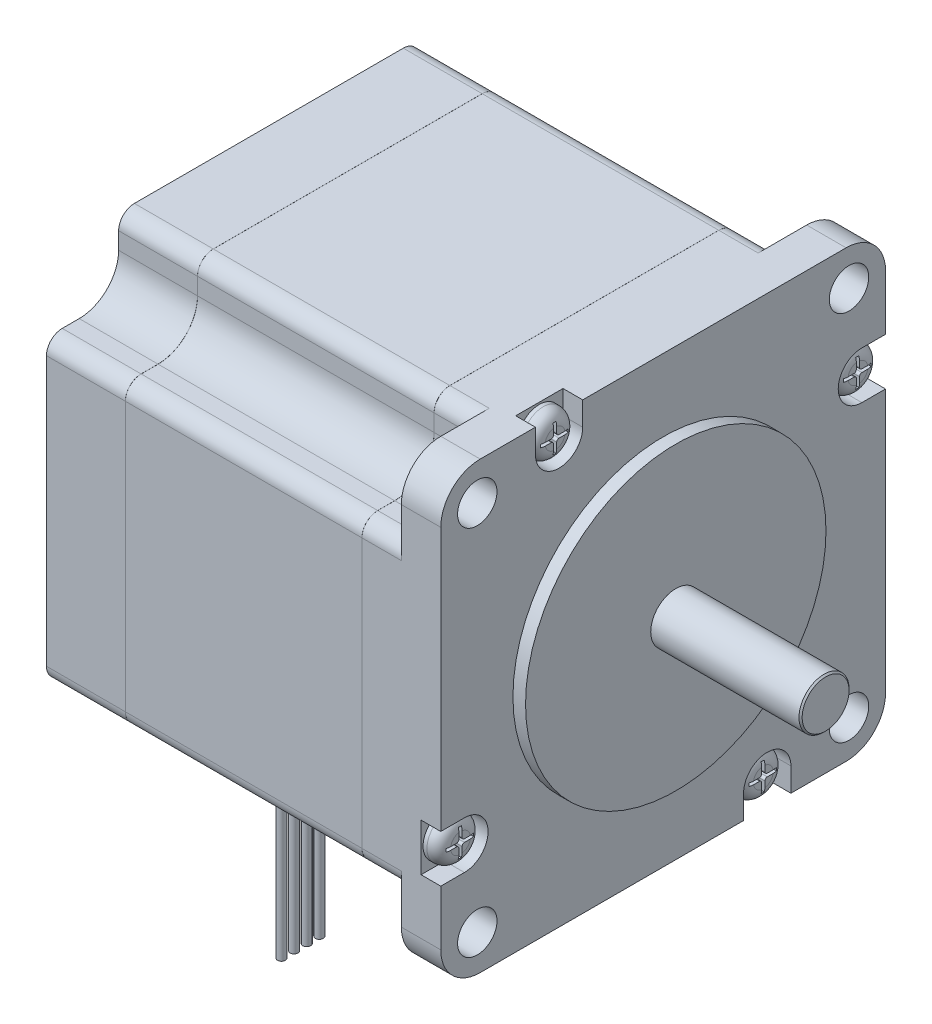
SolidWorks part; units mm, degrees
ref_plane "Front Plane" through (0, 0, 0) normal (0, 0, 1) x (1, 0, 0)
ref_plane "Top Plane" through (0, 0, 0) normal (0, 1, 0) x (1, 0, 0)
ref_plane "Right Plane" through (0, 0, 0) normal (1, 0, 0) x (0, 0, -1)
ref_axis "Axis_X" through (-43.03, 0, 0) along (1, 0, 0)
ref_axis "Axis_Y" through (0, 32.61, 0) along (0, -1, 0)
ref_axis "Axis_Z" through (0, 0, -31.02) along (0, 0, 1)
sketch "Sketch1" plane through (0, 0, 0) normal (1, 0, 0) x (0, 0, -1)
  line L1 (23.2, -28.2) -> (-23.2, -28.2)
  line L2 (28.2, -23.2) -> (28.2, 23.2)
  line L3 (23.2, 28.2) -> (-23.2, 28.2)
  line L4 (-28.2, -23.2) -> (-28.2, 23.2)
  line L5 (28.2, -28.2) -> (-28.2, 28.2) construction
  line L6 (28.2, 28.2) -> (-28.2, -28.2) construction
  arc A0 (28.2, -23.2) -> (23.2, -28.2) centre (23.2, -23.2) cw
  arc A1 (-23.2, -28.2) -> (-28.2, -23.2) centre (-23.2, -23.2) cw
  arc A2 (28.2, 23.2) -> (23.2, 28.2) centre (23.2, 23.2) ccw
  arc A3 (-28.2, 23.2) -> (-23.2, 28.2) centre (-23.2, 23.2) cw
  point P0 (0, 0)
  dimension "FIX_2" = 5
  dimension "FIX_1" = 56.4
extrude "Boss-Extrude1" add sketch "Sketch1" against normal blind 50
sketch "Sketch2" plane through (0, 0, 0) normal (0, 0, 1) x (1, 0, 0)
  line L0 (0, 0) -> (20.6, 0) construction
  line L1 (20.4, 3.175) -> (20.6, 2.975)
  line L2 (0, 0) -> (20.6, 0)
  line L3 (0, 0) -> (0, 19.05)
  line L4 (0, 19.05) -> (1.6, 19.05)
  line L5 (1.6, 3.175) -> (1.6, 19.05)
  line L6 (1.6, 3.175) -> (20.4, 3.175)
  line L9 (20.6, 2.975) -> (20.6, 0)
  dimension "FIX_3" = 38.1
  dimension "FIX_4" = 6.35
  dimension "FIX_5" = 1.6
  dimension "FIX_6" = 20.6
  dimension "FIX_7" = 45
  dimension "FIX_8" = 0.2
revolve "Revolve1" add sketch "Sketch2" angle 360 about axis through (-43.03, 0, 0) along (1, 0, 0)
ref_plane "Plane1" through (-10, 0, 0) normal (1, 0, 0) x (0, 0, -1)
sketch "Sketch3" plane through (-50, 0, 0) normal (-1, 0, 0) x (0, 0, 1)
  line L0 (0, 28.2) -> (0, 0) construction
  line L1 (-28.2, -23.2) -> (-28.2, 23.2) construction
  line L2 (0, 0) -> (-28.2, 0) construction
  line L3 (-23.2, 28.2) -> (23.2, 28.2) construction
  line L4 (19.05, 26.2) -> (19.05, 24.05)
  line L5 (-28.2, 28.2) -> (-17.05, 28.2)
  line L6 (-28.2, 28.2) -> (-28.2, 17.05)
  line L7 (-26.2, 19.05) -> (-24.05, 19.05)
  line L8 (-19.05, 26.2) -> (-19.05, 24.05)
  line L9 (26.2, 19.05) -> (24.05, 19.05)
  line L10 (28.2, 28.2) -> (28.2, 17.05)
  line L11 (28.2, 28.2) -> (17.05, 28.2)
  line L12 (28.2, -28.2) -> (17.05, -28.2)
  line L13 (28.2, -28.2) -> (28.2, -17.05)
  line L14 (26.2, -19.05) -> (24.05, -19.05)
  line L15 (-19.05, -26.2) -> (-19.05, -24.05)
  line L16 (-26.2, -19.05) -> (-24.05, -19.05)
  line L17 (-28.2, -28.2) -> (-28.2, -17.05)
  line L18 (-28.2, -28.2) -> (-17.05, -28.2)
  line L19 (19.05, -26.2) -> (19.05, -24.05)
  arc A0 (-19.05, 24.05) -> (-24.05, 19.05) centre (-24.05, 24.05) cw
  arc A1 (-28.2, 17.05) -> (-26.2, 19.05) centre (-26.2, 17.05) cw
  arc A2 (19.05, 26.2) -> (17.05, 28.2) centre (17.05, 26.2) ccw
  arc A3 (28.2, 17.05) -> (26.2, 19.05) centre (26.2, 17.05) ccw
  arc A4 (-19.05, 26.2) -> (-17.05, 28.2) centre (-17.05, 26.2) cw
  arc A5 (19.05, 24.05) -> (24.05, 19.05) centre (24.05, 24.05) ccw
  arc A6 (19.05, -24.05) -> (24.05, -19.05) centre (24.05, -24.05) cw
  arc A7 (-19.05, -26.2) -> (-17.05, -28.2) centre (-17.05, -26.2) ccw
  arc A8 (28.2, -17.05) -> (26.2, -19.05) centre (26.2, -17.05) cw
  arc A9 (19.05, -26.2) -> (17.05, -28.2) centre (17.05, -26.2) cw
  arc A10 (-28.2, -17.05) -> (-26.2, -19.05) centre (-26.2, -17.05) ccw
  arc A11 (-19.05, -24.05) -> (-24.05, -19.05) centre (-24.05, -24.05) ccw
  point P23 (19.05, 19.05)
  point P26 (-19.05, 19.05)
  point P52 (-19.05, -19.05)
  point P53 (19.05, -19.05)
  dimension "FIX_12" = 5
  dimension "FIX_13" = 2
  dimension "FIX_11" = 9.15
  dimension "FIX_14" = 9.15
extrude "Cut-Extrude1" cut sketch "Sketch3" against normal offset from surface (45 mm away) 5 up to face at (0, 0, 0)
sketch "Sketch4" plane through (-10, 0, 0) normal (1, 0, 0) x (0, 0, -1)
  line L0 (-17.05, -28.15) -> (17.05, -28.15)
  line L1 (19, -26.2) -> (19, -24.05)
  line L2 (24.05, -19) -> (26.2, -19)
  line L3 (28.15, -17.05) -> (28.15, 17.05)
  line L4 (26.2, 19) -> (24.05, 19)
  line L5 (19, 24.05) -> (19, 26.2)
  line L6 (17.05, 28.15) -> (-17.05, 28.15)
  line L7 (-19, 26.2) -> (-19, 24.05)
  line L8 (-24.05, 19) -> (-26.2, 19)
  line L9 (-28.15, 17.05) -> (-28.15, -17.05)
  line L10 (-26.2, -19) -> (-24.05, -19)
  line L11 (-19, -24.05) -> (-19, -26.2)
  line L12 (-17.05, -28.2) -> (17.05, -28.2)
  line L13 (-19.05, -24.05) -> (-19.05, -26.2)
  line L14 (-26.2, -19.05) -> (-24.05, -19.05)
  line L15 (-28.2, 17.05) -> (-28.2, -17.05)
  line L16 (-24.05, 19.05) -> (-26.2, 19.05)
  line L17 (-19.05, 26.2) -> (-19.05, 24.05)
  line L18 (17.05, 28.2) -> (-17.05, 28.2)
  line L19 (19.05, 24.05) -> (19.05, 26.2)
  line L20 (26.2, 19.05) -> (24.05, 19.05)
  line L21 (28.2, -17.05) -> (28.2, 17.05)
  line L22 (24.05, -19.05) -> (26.2, -19.05)
  line L23 (19.05, -26.2) -> (19.05, -24.05)
  line L24 (-17.05, -28.2) -> (17.05, -28.2)
  line L25 (-19.05, -24.05) -> (-19.05, -26.2)
  line L26 (-26.2, -19.05) -> (-24.05, -19.05)
  line L27 (-28.2, 17.05) -> (-28.2, -17.05)
  line L28 (-24.05, 19.05) -> (-26.2, 19.05)
  line L29 (-19.05, 26.2) -> (-19.05, 24.05)
  line L30 (17.05, 28.2) -> (-17.05, 28.2)
  line L31 (19.05, 24.05) -> (19.05, 26.2)
  line L32 (26.2, 19.05) -> (24.05, 19.05)
  line L33 (28.2, -17.05) -> (28.2, 17.05)
  line L34 (24.05, -19.05) -> (26.2, -19.05)
  line L35 (19.05, -26.2) -> (19.05, -24.05)
  arc A0 (17.05, -28.15) -> (19, -26.2) centre (17.05, -26.2) ccw
  arc A1 (24.05, -19) -> (19, -24.05) centre (24.05, -24.05) ccw
  arc A2 (26.2, -19) -> (28.15, -17.05) centre (26.2, -17.05) ccw
  arc A3 (28.15, 17.05) -> (26.2, 19) centre (26.2, 17.05) ccw
  arc A4 (19, 24.05) -> (24.05, 19) centre (24.05, 24.05) ccw
  arc A5 (19, 26.2) -> (17.05, 28.15) centre (17.05, 26.2) ccw
  arc A6 (-17.05, 28.15) -> (-19, 26.2) centre (-17.05, 26.2) ccw
  arc A7 (-24.05, 19) -> (-19, 24.05) centre (-24.05, 24.05) ccw
  arc A8 (-26.2, 19) -> (-28.15, 17.05) centre (-26.2, 17.05) ccw
  arc A9 (-28.15, -17.05) -> (-26.2, -19) centre (-26.2, -17.05) ccw
  arc A10 (-19, -24.05) -> (-24.05, -19) centre (-24.05, -24.05) ccw
  arc A11 (-19, -26.2) -> (-17.05, -28.15) centre (-17.05, -26.2) ccw
  arc A12 (17.05, -28.2) -> (19.05, -26.2) centre (17.05, -26.2) ccw
  arc A13 (-19.05, -26.2) -> (-17.05, -28.2) centre (-17.05, -26.2) ccw
  arc A14 (-19.05, -24.05) -> (-24.05, -19.05) centre (-24.05, -24.05) ccw
  arc A15 (-28.2, -17.05) -> (-26.2, -19.05) centre (-26.2, -17.05) ccw
  arc A16 (-26.2, 19.05) -> (-28.2, 17.05) centre (-26.2, 17.05) ccw
  arc A17 (-24.05, 19.05) -> (-19.05, 24.05) centre (-24.05, 24.05) ccw
  arc A18 (-17.05, 28.2) -> (-19.05, 26.2) centre (-17.05, 26.2) ccw
  arc A19 (19.05, 26.2) -> (17.05, 28.2) centre (17.05, 26.2) ccw
  arc A20 (19.05, 24.05) -> (24.05, 19.05) centre (24.05, 24.05) ccw
  arc A21 (28.2, 17.05) -> (26.2, 19.05) centre (26.2, 17.05) ccw
  arc A22 (26.2, -19.05) -> (28.2, -17.05) centre (26.2, -17.05) ccw
  arc A23 (24.05, -19.05) -> (19.05, -24.05) centre (24.05, -24.05) ccw
  arc A24 (17.05, -28.2) -> (19.05, -26.2) centre (17.05, -26.2) ccw
  arc A25 (-19.05, -26.2) -> (-17.05, -28.2) centre (-17.05, -26.2) ccw
  arc A26 (-19.05, -24.05) -> (-24.05, -19.05) centre (-24.05, -24.05) ccw
  arc A27 (-28.2, -17.05) -> (-26.2, -19.05) centre (-26.2, -17.05) ccw
  arc A28 (-26.2, 19.05) -> (-28.2, 17.05) centre (-26.2, 17.05) ccw
  arc A29 (-24.05, 19.05) -> (-19.05, 24.05) centre (-24.05, 24.05) ccw
  arc A30 (-17.05, 28.2) -> (-19.05, 26.2) centre (-17.05, 26.2) ccw
  arc A31 (19.05, 26.2) -> (17.05, 28.2) centre (17.05, 26.2) ccw
  arc A32 (19.05, 24.05) -> (24.05, 19.05) centre (24.05, 24.05) ccw
  arc A33 (28.2, 17.05) -> (26.2, 19.05) centre (26.2, 17.05) ccw
  arc A34 (26.2, -19.05) -> (28.2, -17.05) centre (26.2, -17.05) ccw
  arc A35 (24.05, -19.05) -> (19.05, -24.05) centre (24.05, -24.05) ccw
  dimension "FIX_16" = 0
  dimension "FIX_17" = 0.05
ref_plane "Plane2" through (-40, 0, 0) normal (-1, 0, 0) x (0, 0, 1)
extrude "Cut-Extrude2" cut sketch "Sketch4" along normal blind 0.01
sketch "Sketch5" plane through (-40, 0, 0) normal (-1, 0, 0) x (0, 0, 1)
  line L12 (-26.2, -19.05) -> (-24.05, -19.05)
  line L13 (-28.2, 17.05) -> (-28.2, -17.05)
  line L14 (-24.05, 19.05) -> (-26.2, 19.05)
  line L15 (-19.05, 26.2) -> (-19.05, 24.05)
  line L16 (17.05, 28.2) -> (-17.05, 28.2)
  line L17 (19.05, 24.05) -> (19.05, 26.2)
  line L18 (26.2, 19.05) -> (24.05, 19.05)
  line L19 (28.2, -17.05) -> (28.2, 17.05)
  line L20 (24.05, -19.05) -> (26.2, -19.05)
  line L21 (19.05, -26.2) -> (19.05, -24.05)
  line L22 (-17.05, -28.2) -> (17.05, -28.2)
  line L23 (-19.05, -24.05) -> (-19.05, -26.2)
  line L24 (-26.2, -19.05) -> (-24.05, -19.05)
  line L25 (-28.2, 17.05) -> (-28.2, -17.05)
  line L26 (-24.05, 19.05) -> (-26.2, 19.05)
  line L27 (-19.05, 26.2) -> (-19.05, 24.05)
  line L28 (17.05, 28.2) -> (-17.05, 28.2)
  line L29 (19.05, 24.05) -> (19.05, 26.2)
  line L30 (26.2, 19.05) -> (24.05, 19.05)
  line L31 (28.2, -17.05) -> (28.2, 17.05)
  line L32 (24.05, -19.05) -> (26.2, -19.05)
  line L33 (19.05, -26.2) -> (19.05, -24.05)
  line L34 (-17.05, -28.2) -> (17.05, -28.2)
  line L35 (-19.05, -24.05) -> (-19.05, -26.2)
  line L36 (28.15, -17.05) -> (28.15, 17.05)
  line L37 (26.2, 19) -> (24.05, 19)
  line L38 (19, 24.05) -> (19, 26.2)
  line L39 (17.05, 28.15) -> (-17.05, 28.15)
  line L40 (-19, 26.2) -> (-19, 24.05)
  line L41 (-24.05, 19) -> (-26.2, 19)
  line L42 (-28.15, 17.05) -> (-28.15, -17.05)
  line L43 (-26.2, -19) -> (-24.05, -19)
  line L44 (-19, -24.05) -> (-19, -26.2)
  line L45 (-17.05, -28.15) -> (17.05, -28.15)
  line L46 (19, -26.2) -> (19, -24.05)
  line L47 (24.05, -19) -> (26.2, -19)
  line L48 (28.15, -17.05) -> (28.15, 17.05)
  line L49 (26.2, 19) -> (24.05, 19)
  line L50 (19, 24.05) -> (19, 26.2)
  line L51 (17.05, 28.15) -> (-17.05, 28.15)
  line L52 (-19, 26.2) -> (-19, 24.05)
  line L53 (-24.05, 19) -> (-26.2, 19)
  line L54 (-28.15, 17.05) -> (-28.15, -17.05)
  line L55 (-26.2, -19) -> (-24.05, -19)
  line L56 (-19, -24.05) -> (-19, -26.2)
  line L57 (-17.05, -28.15) -> (17.05, -28.15)
  line L58 (19, -26.2) -> (19, -24.05)
  line L59 (24.05, -19) -> (26.2, -19)
  arc A12 (-28.2, -17.05) -> (-26.2, -19.05) centre (-26.2, -17.05) ccw
  arc A13 (-26.2, 19.05) -> (-28.2, 17.05) centre (-26.2, 17.05) ccw
  arc A14 (-24.05, 19.05) -> (-19.05, 24.05) centre (-24.05, 24.05) ccw
  arc A15 (-17.05, 28.2) -> (-19.05, 26.2) centre (-17.05, 26.2) ccw
  arc A16 (19.05, 26.2) -> (17.05, 28.2) centre (17.05, 26.2) ccw
  arc A17 (19.05, 24.05) -> (24.05, 19.05) centre (24.05, 24.05) ccw
  arc A18 (28.2, 17.05) -> (26.2, 19.05) centre (26.2, 17.05) ccw
  arc A19 (26.2, -19.05) -> (28.2, -17.05) centre (26.2, -17.05) ccw
  arc A20 (24.05, -19.05) -> (19.05, -24.05) centre (24.05, -24.05) ccw
  arc A21 (17.05, -28.2) -> (19.05, -26.2) centre (17.05, -26.2) ccw
  arc A22 (-19.05, -26.2) -> (-17.05, -28.2) centre (-17.05, -26.2) ccw
  arc A23 (-19.05, -24.05) -> (-24.05, -19.05) centre (-24.05, -24.05) ccw
  arc A24 (-28.2, -17.05) -> (-26.2, -19.05) centre (-26.2, -17.05) ccw
  arc A25 (-26.2, 19.05) -> (-28.2, 17.05) centre (-26.2, 17.05) ccw
  arc A26 (-24.05, 19.05) -> (-19.05, 24.05) centre (-24.05, 24.05) ccw
  arc A27 (-17.05, 28.2) -> (-19.05, 26.2) centre (-17.05, 26.2) ccw
  arc A28 (19.05, 26.2) -> (17.05, 28.2) centre (17.05, 26.2) ccw
  arc A29 (19.05, 24.05) -> (24.05, 19.05) centre (24.05, 24.05) ccw
  arc A30 (28.2, 17.05) -> (26.2, 19.05) centre (26.2, 17.05) ccw
  arc A31 (26.2, -19.05) -> (28.2, -17.05) centre (26.2, -17.05) ccw
  arc A32 (24.05, -19.05) -> (19.05, -24.05) centre (24.05, -24.05) ccw
  arc A33 (17.05, -28.2) -> (19.05, -26.2) centre (17.05, -26.2) ccw
  arc A34 (-19.05, -26.2) -> (-17.05, -28.2) centre (-17.05, -26.2) ccw
  arc A35 (-19.05, -24.05) -> (-24.05, -19.05) centre (-24.05, -24.05) ccw
  arc A36 (28.15, 17.05) -> (26.2, 19) centre (26.2, 17.05) ccw
  arc A37 (19, 24.05) -> (24.05, 19) centre (24.05, 24.05) ccw
  arc A38 (19, 26.2) -> (17.05, 28.15) centre (17.05, 26.2) ccw
  arc A39 (-17.05, 28.15) -> (-19, 26.2) centre (-17.05, 26.2) ccw
  arc A40 (-24.05, 19) -> (-19, 24.05) centre (-24.05, 24.05) ccw
  arc A41 (-26.2, 19) -> (-28.15, 17.05) centre (-26.2, 17.05) ccw
  arc A42 (-28.15, -17.05) -> (-26.2, -19) centre (-26.2, -17.05) ccw
  arc A43 (-19, -24.05) -> (-24.05, -19) centre (-24.05, -24.05) ccw
  arc A44 (-19, -26.2) -> (-17.05, -28.15) centre (-17.05, -26.2) ccw
  arc A45 (17.05, -28.15) -> (19, -26.2) centre (17.05, -26.2) ccw
  arc A46 (24.05, -19) -> (19, -24.05) centre (24.05, -24.05) ccw
  arc A47 (26.2, -19) -> (28.15, -17.05) centre (26.2, -17.05) ccw
  arc A48 (28.15, 17.05) -> (26.2, 19) centre (26.2, 17.05) ccw
  arc A49 (19, 24.05) -> (24.05, 19) centre (24.05, 24.05) ccw
  arc A50 (19, 26.2) -> (17.05, 28.15) centre (17.05, 26.2) ccw
  arc A51 (-17.05, 28.15) -> (-19, 26.2) centre (-17.05, 26.2) ccw
  arc A52 (-24.05, 19) -> (-19, 24.05) centre (-24.05, 24.05) ccw
  arc A53 (-26.2, 19) -> (-28.15, 17.05) centre (-26.2, 17.05) ccw
  arc A54 (-28.15, -17.05) -> (-26.2, -19) centre (-26.2, -17.05) ccw
  arc A55 (-19, -24.05) -> (-24.05, -19) centre (-24.05, -24.05) ccw
  arc A56 (-19, -26.2) -> (-17.05, -28.15) centre (-17.05, -26.2) ccw
  arc A57 (17.05, -28.15) -> (19, -26.2) centre (17.05, -26.2) ccw
  arc A58 (24.05, -19) -> (19, -24.05) centre (24.05, -24.05) ccw
  arc A59 (26.2, -19) -> (28.15, -17.05) centre (26.2, -17.05) ccw
  dimension "FIX_20" = 0
  dimension "FIX_21" = 0
extrude "Cut-Extrude3" cut sketch "Sketch5" against normal blind 0.01
sketch "Sketch6" plane through (0, 0, 0) normal (1, 0, 0) x (0, 0, -1)
  line L0 (-13.2, 25.2) -> (-13.2, 28.2) construction
  line L1 (-16.2, 25.2) -> (-16.2, 28.2)
  line L2 (-10.2, 25.2) -> (-10.2, 28.2)
  line L3 (-28.2, 23.2) -> (-28.2, -23.2) construction
  line L4 (23.2, 28.2) -> (-23.2, 28.2) construction
  line L5 (25.2, 13.2) -> (28.2, 13.2) construction
  line L6 (25.2, 16.2) -> (28.2, 16.2)
  line L7 (25.2, 10.2) -> (28.2, 10.2)
  line L8 (13.2, -25.2) -> (13.2, -28.2) construction
  line L9 (16.2, -25.2) -> (16.2, -28.2)
  line L10 (10.2, -25.2) -> (10.2, -28.2)
  line L11 (-25.2, -13.2) -> (-28.2, -13.2) construction
  line L12 (-25.2, -16.2) -> (-28.2, -16.2)
  line L13 (-25.2, -10.2) -> (-28.2, -10.2)
  arc A0 (-16.2, 25.2) -> (-10.2, 25.2) centre (-13.2, 25.2) ccw
  arc A1 (-10.2, 28.2) -> (-16.2, 28.2) centre (-13.2, 28.2) ccw
  arc A2 (25.2, 16.2) -> (25.2, 10.2) centre (25.2, 13.2) ccw
  arc A3 (28.2, 10.2) -> (28.2, 16.2) centre (28.2, 13.2) ccw
  arc A4 (16.2, -25.2) -> (10.2, -25.2) centre (13.2, -25.2) ccw
  arc A5 (10.2, -28.2) -> (16.2, -28.2) centre (13.2, -28.2) ccw
  arc A6 (-25.2, -16.2) -> (-25.2, -10.2) centre (-25.2, -13.2) ccw
  arc A7 (-28.2, -10.2) -> (-28.2, -16.2) centre (-28.2, -13.2) ccw
  point P2 (-13.2, 26.7)
  point P16 (26.7, 13.2)
  point P23 (13.2, -26.7)
  point P30 (-26.7, -13.2)
  point P35 (0, 0)
  dimension "FIX_23" = 3
  dimension "FIX_24" = 15
  dimension "FIX_25" = 3
  dimension "FIX_26" = 4
extrude "Cut-Extrude4" cut sketch "Sketch6" against normal blind 2.5
ref_plane "Plane3" through (0, 25.2, 0) normal (0, 1, 0) x (1, 0, 0)
sketch "Sketch7" plane through (0, 25.2, 0) normal (0, 1, 0) x (1, 0, 0)
  line L0 (0, -13.2) -> (-2.5, -13.2) construction
  line L1 (0, -16.2) -> (0, -10.2) construction
  line L2 (-2.5, -16.2) -> (-2.5, -10.2) construction
  line L4 (-2.5, -13.2) -> (-0.5, -13.2)
  line L5 (-2.5, -13.2) -> (-2.5, -15.95)
  line L6 (-2.5, -15.95) -> (-2, -15.95)
  line L7 (-0.5, -13.2) -> (-0.5, -14.45)
  arc A0 (-0.5, -14.45) -> (-2, -15.95) centre (-2, -14.45) cw
  dimension "FIX_30" = 1.5
  dimension "FIX_31" = 5.5
  dimension "FIX_29" = 2
revolve "Revolve2" add sketch "Sketch7" angle 360 about L0
sketch "Sketch8" plane through (-0.5, 0, 0) normal (1, 0, 0) x (0, 0, -1)
  line L1 (-14.95, 25.4) -> (-13.7, 25.4)
  line L2 (-14.95, 25.4) -> (-14.95, 25)
  line L3 (-14.95, 25) -> (-13.7, 25)
  line L4 (-11.45, 25.4) -> (-11.45, 25)
  line L5 (-14.95, 25.4) -> (-11.45, 25) construction
  line L6 (-14.95, 25) -> (-11.45, 25.4) construction
  line L7 (-13.4, 26.95) -> (-13, 26.95)
  line L8 (-13.4, 26.95) -> (-13.4, 25.7)
  line L9 (-13.4, 23.45) -> (-13, 23.45)
  line L10 (-13, 26.95) -> (-13, 25.7)
  line L11 (-13.4, 26.95) -> (-13, 23.45) construction
  line L12 (-13.4, 23.45) -> (-13, 26.95) construction
  line L14 (-13.4, 24.7) -> (-13.4, 23.45)
  line L15 (-12.7, 25.4) -> (-11.45, 25.4)
  line L17 (-13, 24.7) -> (-13, 23.45)
  line L18 (-12.7, 25) -> (-11.45, 25)
  arc A0 (-13.7, 25) -> (-13.4, 24.7) centre (-13.7, 24.7) cw
  arc A1 (-13, 24.7) -> (-12.7, 25) centre (-12.7, 24.7) cw
  arc A2 (-12.7, 25.4) -> (-13, 25.7) centre (-12.7, 25.7) cw
  arc A3 (-13.4, 25.7) -> (-13.7, 25.4) centre (-13.7, 25.7) cw
  point P0 (-13.2, 25.2)
  point P6 (-13.2, 25.2)
  point P18 (-13, 25)
  dimension "FIX_35" = 0.3
  dimension "FIX_33" = 3.5
  dimension "FIX_34" = 0.4
extrude "Cut-Extrude5" cut sketch "Sketch8" against normal blind 1
pattern_circular "CirPattern1" count 4 over 360 about axis through (1.6, 0, 0) along (-1, 0, 0) of "Cut-Extrude5", "Revolve2"
hole_wizard "DiameterHole1" positions "Sketch9" profile "Sketch10" hole size "Ø5.0" standard "JIS" end condition through all
sketch "Sketch9" plane through (0, 0, 0) normal (1, 0, 0) x (0, 0, -1)
  line L1 (-23.57, 23.57) -> (23.57, -23.57) construction
  line L3 (-23.57, -23.57) -> (23.57, 23.57) construction
  point P0 (-23.57, 23.57)
  point P2 (23.57, 23.57)
  point P4 (23.57, -23.57)
  point P6 (-23.57, -23.57)
  dimension "FIX_40" = 47.14
  dimension "FIX_41" = 47.14
sketch "Sketch10" plane through (0, 23.57, 23.57) normal (0, 1, 0) x (0, 0, -1)
  line L0 (0, 0) -> (0, 50)
  line L1 (0, 50) -> (2.5, 50)
  line L2 (2.5, 50) -> (2.5, 0)
  line L5 (2.5, 0) -> (0, 0)
  line L11 (0, 0) -> (0, 50) construction
  dimension "FIX_39" = 5
  dimension "Thru Hole Depth" = 50
sketch "Sketch11" plane through (0, -28.2, 0) normal (0, -1, 0) x (1, 0, 0)
  line L0 (-50, 17.05) -> (-50, -17.05) construction
  line L1 (-48, 4) -> (-44, 4)
  line L2 (-48, 4) -> (-48, -4)
  line L3 (-48, -4) -> (-44, -4)
  line L4 (-44, 4) -> (-44, -4)
  line L5 (0, 0) -> (-44, 0) construction
  dimension "FIX_42" = 4
  dimension "FIX_43" = 8
  dimension "FIX_44" = 2
extrude "Boss-Extrude2" add sketch "Sketch11" along normal blind 1.8
sketch "Sketch12" plane through (0, -30, 0) normal (0, -1, 0) x (1, 0, 0)
  line L0 (-44, 4) -> (-48, 4) construction
  line L1 (-44, 4) -> (-48, 4) construction
  line L2 (-46, 2.4) -> (-46, 4) construction
  circle A0 centre (-46, 2.4) radius 0.5
  circle A1 centre (-46, 0.8) radius 0.5
  circle A2 centre (-46, -0.8) radius 0.5
  circle A3 centre (-46, -2.4) radius 0.5
  dimension "FIX_46" = 1
  dimension "FIX_47" = 1.6
  dimension "FIX_48" = 1.6
  dimension "FIX_49" = 1.6
  dimension "FIX_50" = 1.6
extrude "Boss-Extrude3" add sketch "Sketch12" along normal blind 30
equation "\"Factor\"= 1.082532"
